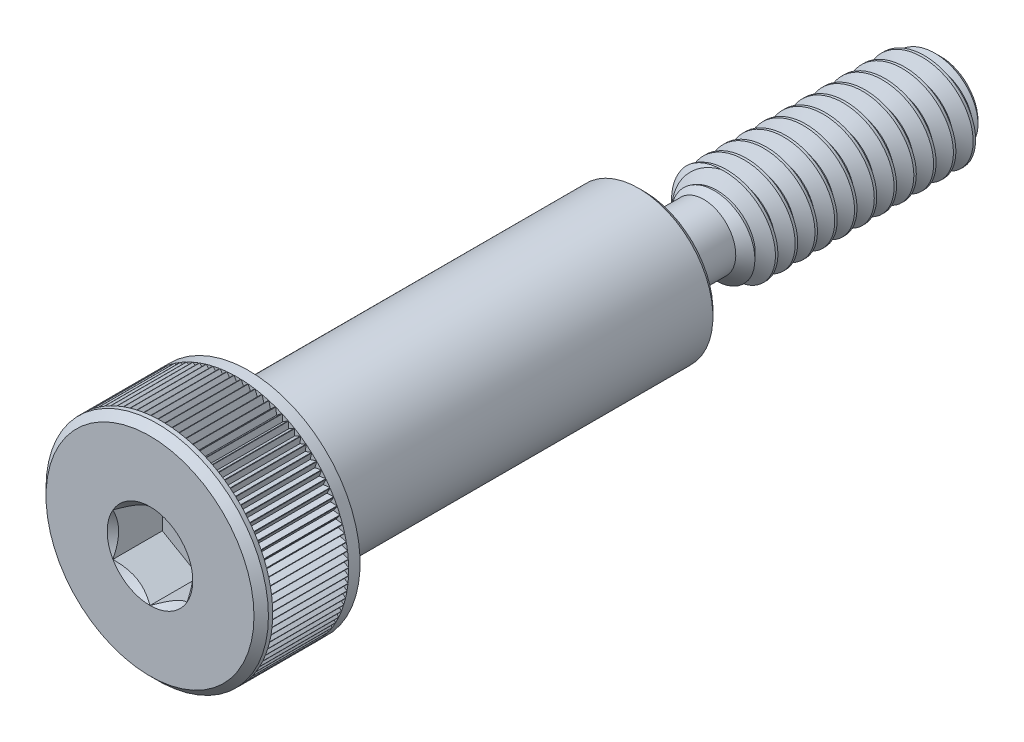
SolidWorks part; units mm, degrees
other "DetailItem1"
other "DetailItem2"
other "DetailItem5"
other "DetailItem6"
ref_plane "Front" through (0, 0, 0) normal (0, 0, 1) x (1, 0, 0)
ref_plane "Top" through (0, 0, 0) normal (0, 1, 0) x (1, 0, 0)
ref_plane "Right" through (0, 0, 0) normal (1, 0, 0) x (0, 0, -1)
sketch "Sketch1" plane through (0, 0, 0) normal (1, 0, 0) x (0, 0, -1)
  line L0 (0, 7.1437) -> (6.35, 7.1437) construction
  line L1 (6.35, 7.1437) -> (6.35, 4.4053) construction
  line L2 (7.9772, 4.7625) -> (31.75, 4.7625) construction
  line L3 (7.9772, -4.7625) -> (31.75, -4.7625) construction
  line L4 (31.75, 3.175) -> (50.8, 3.175) construction
  line L5 (50.8, 3.175) -> (50.8, 0) construction
  line L6 (31.75, 0) -> (0, 0) construction
  line L7 (0, 0) -> (0, 7.1437) construction
  line L8 (0, 7.1437) -> (0, -7.1438) construction
  line L9 (50.8, 3.175) -> (50.8, -3.175) construction
  line L10 (31.75, 4.7625) -> (31.75, -4.7625) construction
  line L11 (50.8, -3.175) -> (49.1222, -3.175) construction
  line L12 (31.75, 4.7625) -> (31.75, 0) construction
  line L13 (6.35, 4.4053) -> (7.62, 4.4053) construction
  line L14 (7.62, 4.4053) -> (7.9772, 4.7625) construction
  line L15 (50.8, 0) -> (31.75, 0) construction
  line L16 (7.62, -4.4053) -> (7.9772, -4.7625) construction
  line L17 (6.35, -4.4053) -> (7.62, -4.4053) construction
  line L18 (0, -7.1438) -> (6.35, -7.1438) construction
  line L19 (6.35, -7.1438) -> (6.35, -4.4053) construction
  line L20 (50.8, 4.7625) -> (48.895, 4.7625) construction
  line L21 (50.8, -4.7625) -> (48.895, -4.7625) construction
  line L22 (50.8, 0) -> (69.85, 0) construction
  line L23 (19.05, 0) -> (19.05, 7.1438) construction
  line L24 (50.8, -4.7625) -> (50.8, 4.7625) construction
  line L25 (0, -2.3813) -> (0, 2.3813) construction
  line L26 (50.7206, 3.3125) -> (51.9906, 3.3125) construction
  line L27 (51.9906, 3.3125) -> (51.3556, 2.2126) construction
  line L28 (51.3556, 2.2126) -> (50.7206, 3.3125) construction
  line L29 (51.3556, 2.2126) -> (51.3556, 2.3501) construction
  line L30 (51.3556, 3.3125) -> (51.3556, 3.175) construction
  line L31 (51.9113, 3.175) -> (50.8, 3.175) construction
  line L32 (51.2763, 2.3501) -> (51.435, 2.3501) construction
  line L33 (51.3556, 3.2437) -> (51.9509, 3.2437) construction
  line L34 (51.3556, 3.2437) -> (50.7603, 3.2437) construction
  line L35 (7.9772, 4.7625) -> (7.9772, -4.7625) construction
  line L36 (31.3928, 4.7625) -> (31.75, 4.4053) construction
  line L37 (31.3928, 4.7625) -> (31.3928, 0) construction
  point P2 (6.985, 0)
  point P8 (48.895, -3.175)
  point P12 (31.75, 0)
  point P15 (31.115, 0)
  point P31 (8.1915, 0)
  point P32 (29.9085, 0)
  point P34 (50.8, 0)
  point P37 (0, 0)
  dimension "D1" = 1.905
  dimension "D2" = 1.6778
  dimension "D3" = 135
  dimension "D4" = 1.27
  dimension "D5" = 0.3572
  dimension "D6" = 12.7
  dimension "D7" = 24.13
  dimension "D8" = 21.717
  dimension "D9" = 0.1588
  dimension "Shoulder Lg" = 25.4
  dimension "D10" = 45
sketch "Sketch13" plane through (0, 0, 0) normal (1, 0, 0) x (0, 0, -1)
  line L0 (0, 0) -> (0, 7.1437)
  line L1 (0, 7.1437) -> (6.35, 7.1437)
  line L2 (6.35, 7.1437) -> (6.35, 4.4053)
  line L3 (6.35, 4.4053) -> (7.62, 4.4053)
  line L4 (31.75, 0) -> (31.75, 4.4053)
  line L5 (7.62, 4.4053) -> (7.9772, 4.7625)
  line L7 (31.75, 4.7625) -> (31.75, 0) construction
  line L8 (31.75, 4.7625) -> (31.75, -4.7625) construction
  line L9 (31.75, 0) -> (0, 0) construction
  line L10 (31.75, 4.4053) -> (31.3928, 4.7625)
  line L12 (7.9772, 4.7625) -> (31.3928, 4.7625)
  line L13 (0, 0) -> (31.75, 0)
  line L14 (7.9772, 4.7625) -> (31.75, 4.7625) construction
  line L18 (50.8, 4.7625) -> (50.8, -4.7625) construction
  dimension "D1" = 25.4
  dimension "D2" = 45
  dimension "D3" = 9.525
revolve "Revolve1" add sketch "Sketch13" angle 360 about L9
sketch "Sketch12" plane through (0, 0, -31.75) normal (0, 0, -1) x (-1, 0, 0)
  circle A0 centre (0, 0) radius 3.175
extrude "Boss-Extrude1" add sketch "Sketch12" along normal up to vertex (19.05 mm away) up to point (0, 0, -50.8)
ref_plane "Plane1" through (0, 0, -50.8) normal (0, 0, 1) x (1, 0, 0)
sketch "Sketch3" plane through (0, 0, -50.8) normal (0, 0, 1) x (1, 0, 0)
  circle A0 centre (0, 0) radius 3.175
sketch "Sketch5" plane through (0, 0, 0) normal (1, 0, 0) x (0, 0, -1)
  line L0 (31.75, 3.175) -> (36.6713, 3.175)
  line L1 (36.6713, 3.175) -> (35.56, 2.0638)
  line L2 (35.56, 2.0638) -> (31.75, 2.0637)
  line L3 (31.75, 3.175) -> (31.75, 2.0637)
  line L4 (31.75, 3.175) -> (50.8, 3.175) construction
  line L5 (31.75, 4.7625) -> (31.75, 0) construction
  line L6 (31.75, 4.7625) -> (31.75, -4.7625) construction
  line L7 (50.8, 0) -> (31.75, 0) construction
  line L8 (50.8, -3.175) -> (50.8, 3.175) construction
  dimension "D4" = 3.81
  dimension "D1" = 45
  dimension "D2" = 15.24
  dimension "D3" = 2.0638
revolve "Cut-Revolve1" cut sketch "Sketch5" angle 360 mid plane about L6
chamfer "Chamfer1" distance 0.7937 angle 45 1 edges at (-3.175, 0, -50.8)
chamfer "Chamfer2" distance 0.4643 angle 45 1 edges at (-7.1437, 0, 0)
fillet "Fillet1" radius 0.3175 1 edges at (0, 2.0637, -31.75)
sketch "Sketch10" plane through (0, 0, 0) normal (1, 0, 0) x (0, 0, -1)
  line L0 (0.4643, 0) -> (5.8857, 0) construction
  line L1 (6.35, -7.1437) -> (6.35, 7.1437) construction
  line L2 (0.4643, -7.1437) -> (0.4643, 7.1437) construction
  line L3 (0.4643, 0) -> (0, 0) construction
  line L4 (5.8857, 0) -> (6.35, 0) construction
  point P6 (3.175, 0)
  dimension "D1" = 5.4213
ref_plane "Plane2" through (0, 0, -3.175) normal (0, 0, 1) x (1, 0, 0)
sketch "Sketch8" plane through (0, 0, 0) normal (0, 0, 1) x (1, 0, 0)
  line L1 (2.3812, 1.3748) -> (0, 2.7496)
  line L2 (0, 2.7496) -> (-2.3813, 1.3748)
  line L3 (-2.3813, 1.3748) -> (-2.3813, -1.3748)
  line L4 (-2.3813, -1.3748) -> (0, -2.7496)
  line L5 (0, -2.7496) -> (2.3812, -1.3748)
  line L6 (2.3812, -1.3748) -> (2.3812, 1.3748)
  circle A0 centre (0, 0) radius 2.3813 construction
extrude "Cut-Extrude2" cut sketch "Sketch8" against normal blind 3.175
sketch "Sketch9" plane through (0, 0, 0) normal (0, 0, 1) x (1, 0, 0)
  circle A0 centre (0, 0) radius 2.7496
extrude "Cut-Extrude4" cut sketch "Sketch9" against normal blind 3.175 draft 45
sketch "Sketch16" plane through (0, 0, 0) normal (0, 1, 0) x (1, 0, 0)
  line L0 (0, 19.05) -> (-4.7625, 19.05) construction
  line L1 (-4.7625, 31.3928) -> (-4.7625, 7.9772) construction
  line L2 (0, 29.9085) -> (-4.7625, 29.9085) construction
  line L3 (0, 19.05) -> (0, 29.9085) construction
  line L4 (0, 24.4793) -> (0, 29.9085) construction
  line L5 (0, 29.9085) -> (0, 27.1939) construction
  line L6 (0, 27.1939) -> (-4.7625, 27.1939) construction
  line L7 (0, 7.9772) -> (-4.7625, 7.9772) construction
  line L8 (-4.7625, 7.9772) -> (4.7625, 7.9772) construction
  line L9 (0, 31.75) -> (4.7625, 31.75) construction
  point P0 (0, 19.05)
  point P2 (0, 29.9085)
  point P11 (0, 7.9772)
sketch "reference 1" plane through (0, 0, -6.35) normal (0, 0, -1) x (-1, 0, 0)
  circle A1 centre (0, 0) radius 7.1437
ref_axis "Center Axis 1" through (0, 0, -7.9772) along (0, 0, -1)
ref_plane "Contact Plane 1" through (0, 0, -50.8) normal (0, 0, -1) x (-1, 0, 0)
ref_plane "Contact Plane 2" through (0, 0, -6.35) normal (0, 0, -1) x (-1, 0, 0)
ref_plane "Plane3" through (0, 0, -31.75) normal (0, 0, 1) x (1, 0, 0)
split "Split1" trim tools "Plane3" bodies to split 118 resulting bodies 127 128
sketch "Sketch15" plane through (0, 0, -50.8) normal (0, 0, -1) x (-1, 0, 0)
  circle A0 centre (0, 0) radius 3.175
curve "Helix/Spiral1" pitch 1.27 height 17.78 radius 3.175 centre (0, 0, -50.8) axis (0, 0, 1) start towards (0, 1, 0)
sketch "Sketch4" plane through (0, 0, 0) normal (1, 0, 0) x (0, 0, -1)
  line L0 (51.2763, 2.3501) -> (51.435, 2.3501) construction
  line L1 (51.9906, 3.3125) -> (51.3556, 2.2126) construction
  line L3 (51.3556, 3.2437) -> (51.9509, 3.2437) construction
  line L4 (51.3556, 3.2437) -> (50.7603, 3.2437) construction
  line L5 (51.3556, 2.2126) -> (50.7206, 3.3125) construction
  line L6 (51.2763, 2.3501) -> (51.435, 2.3501)
  line L7 (51.9509, 3.2437) -> (51.435, 2.3501)
  line L8 (51.3556, 3.2437) -> (51.9509, 3.2437)
  line L9 (51.3556, 3.2437) -> (50.7603, 3.2437)
  line L10 (51.2763, 2.3501) -> (50.7603, 3.2437)
sweep "Cut-Sweep1" cut profiles "Sketch4" path "Helix/Spiral1" align with end faces yes
sketch "Sketch14" plane through (0, 0, -31.75) normal (0, 0, -1) x (-1, 0, 0)
  line L0 (0, -4.7625) -> (0, 4.7625) construction
  circle A0 centre (0, 0) radius 1.5875
  dimension "D1" = 3.175
extrude "Boss-Extrude2" add sketch "Sketch14" along normal up to vertex (17.145 mm away) up to point (0, 4.7625, -48.895)
sketch "Sketch11" plane through (0, 0, -3.175) normal (0, 0, 1) x (1, 0, 0)
  line L0 (0, 6.7723) -> (0, 7.1437) construction
  line L1 (0, 6.7723) -> (0.2145, 7.1437)
  line L2 (0, 6.7723) -> (-0.2145, 7.1437)
  line L3 (-0.2145, 7.1437) -> (0.2145, 7.1437)
  line L4 (0, 0) -> (-0.2145, 7.1437) construction
  line L5 (0.2145, 7.1437) -> (0, 0) construction
  circle A2 centre (0, 0) radius 7.1437 construction
  point P8 (2.3908, 0.7309)
  dimension "D1" = 0.3715
  dimension "D2" = 3.439
extrude "Cut-Extrude5" cut sketch "Sketch11" along normal blind 2.4396 and the other way blind 2.4396
pattern_circular "CirPattern1" count 99 over 360 about axis through (0, 0, -31.75) along (0, 0, 1) of "Cut-Extrude5" reverse direction yes
equation "\"D1@Chamfer1\" = \"Thread Dia@Sketch1\" * .125"
equation "\"D1@Cut-Extrude2\"= \"Head Ht@Sketch1\" * .5"
equation "\"D1@Cut-Extrude4\" = \"D1@Cut-Extrude2\""
equation "\"D1@Chamfer2\"=\"Head Dia@Sketch1\" * .0325"
equation "\"D1@Sketch1\"=\"Pitch@Sketch1\"*1.5"
equation "\"D1@Sketch11\"=\"D1@Chamfer2\"*.8"
equation "\"D4@Sketch5\"=\"Thread Lg@Sketch1\"*0.2"
equation "\"D3@Sketch5\"=(\"Thread Dia@Sketch1\"*0.65)/2"
equation "\"D1@Fillet1\"=\"Pitch@Sketch1\"*.25"
equation "\"D1@Cut-Extrude5\"=\"D1@Sketch10\"*.45"
equation "\"D1@CirPattern1\"=(360/(\"D2@Sketch11\"))-6"
equation "\"D4@Sketch1\"=\"Head Ht@Sketch1\"*0.2"
equation "\"D5@Sketch1\"=\"Head Dia@Sketch1\"*0.025"
equation "\"D6@Sketch1\"=\"Shoulder Lg@Sketch1\"/2"
equation "\"D7@Sketch1\"=\"Shoulder Lg@Sketch1\"*0.95"
equation "\"D8@Sketch1\"=\"D7@Sketch1\"*0.9"
equation "\"D2@Cut-Extrude5\"=\"D1@Sketch10\"*.45"
equation "\"D9@Sketch1\"=\"Pitch@Sketch1\"/8"
equation "\"D1@Sketch14\"=\"Thread Dia@Sketch1\"*.5"
equation "\"D4@Helix/Spiral1\"=\"Pitch@Sketch1\""
equation "\"D3@Helix/Spiral1\"=\"Thread Lg@Sketch1\"-\"Pitch@Sketch1\""
